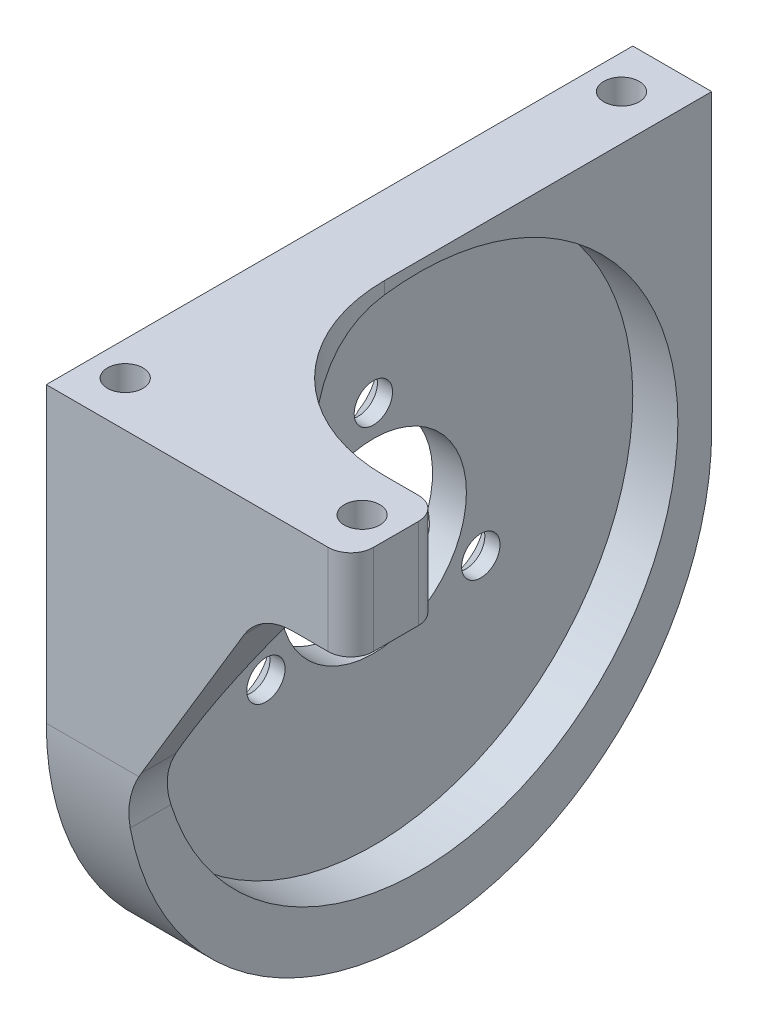
SolidWorks part; units mm, degrees
ref_plane "Plano frontal" through (0, 0, 0) normal (0, 0, 1) x (1, 0, 0)
ref_plane "Plano superior" through (0, 0, 0) normal (0, 1, 0) x (1, 0, 0)
ref_plane "Plano direito" through (0, 0, 0) normal (1, 0, 0) x (0, 0, -1)
sketch "Esboço1" plane through (0, 0, 0) normal (1, 0, 0) x (0, 0, -1)
  line L1 (0, 0) -> (52, 0)
  line L2 (0, 0) -> (0, 52)
  line L3 (0, 52) -> (52, 52)
  line L4 (52, 0) -> (52, 52)
  dimension "D1" = 52
  dimension "D2" = 52
extrude "Ressalto-extrusão1" add sketch "Esboço1" along normal blind 7
sketch "Esboço2" plane through (0, 0, 0) normal (-1, 0, 0) x (0, 0, 1)
  line L1 (-26, 52) -> (-26, 28.1)
  line L2 (-52, 52) -> (0, 52) construction
  circle A0 centre (-26, 28.1) radius 8.25
  dimension "D1" = 16.5
  dimension "D3" = 23.9
extrude "Corte-extrusão1" cut sketch "Esboço2" against normal through all contours A0
sketch "Esboço6" plane through (0, 0, 0) normal (-1, 0, 0) x (0, 0, 1)
  line L1 (-26, 52) -> (-26, 39.1)
  line L2 (-52, 52) -> (0, 52) construction
  circle A0 centre (-26, 28.1) radius 8.25 construction
  point P0 (-26, 39.1)
  dimension "D1" = 11
hole_wizard "Escareado para SFHCS M31" positions "Esboço13" profile "Esboço14" countersink size "M3" standard "Ansi Metric" end condition up to next
sketch "Esboço13" plane through (0, 0, 0) normal (-1, 0, 0) x (0, 0, 1)
  point P0 (-26, 39.1)
sketch "Esboço14" plane through (0, 39.1, -26) normal (0, 1, 0) x (0, 0, 1)
  line L0 (0, 0) -> (0, 7)
  line L1 (0, 7) -> (1.7, 7)
  line L2 (1.7, 7) -> (1.7, 1.66)
  line L3 (1.7, 1.66) -> (3.36, 0)
  line L5 (3.36, 0) -> (0, 0)
  line L6 (-1.7, 1.66) -> (-3.36, 0) construction
  line L11 (0, -6.35) -> (0, 107.95) construction
  dimension "Thru Hole Dia." = 3.4
  dimension "Thru Hole Depth" = 7
  dimension "Near C'Sink Dia." = 6.72
  dimension "Near C'Sink Angle" = 90
pattern_circular "PadrãoCircular1" count 3 over 360 about axis through (0, 28.1, -26) along (-1, 0, 0) of "Escareado para SFHCS M31"
sketch "Esboço27" plane through (7, 0, 0) normal (1, 0, 0) x (0, 0, -1)
  circle A0 centre (26, 28.1) radius 23
  dimension "D1" = 46
extrude "Corte-extrusão5" cut sketch "Esboço27" against normal blind 4
fillet "Filete1" radius 26 2 edges at (3.5, 0, -52) (3.5, 0, 0)
hole_wizard "Furo roscado para conduíte de M3x0.51" positions "Esboço33" profile "Esboço34" tap size "M3x0.5" standard "Helicoil® Metric"
sketch "Esboço33" plane through (0, 52, 0) normal (0, 1, 0) x (1, 0, 0)
  line L0 (0, 52) -> (0, 0) construction
  line L1 (7, 52) -> (0, 52) construction
  line L2 (7, 0) -> (0, 0) construction
  point P0 (3, 48)
  point P2 (3, 4)
  dimension "D1" = 3
  dimension "D2" = 4
  dimension "D3" = 3
  dimension "D4" = 4
cosmetic thread "Rosca de furo1"
cosmetic thread "Rosca de furo2"
sketch "Esboço34" plane through (3, 52, -48) normal (1, 0, 0) x (0, 0, 1)
  line L0 (0, 0) -> (0, 10.9464)
  line L1 (0, 10.9464) -> (1.575, 10)
  line L2 (1.575, 10) -> (1.575, 0)
  line L5 (1.575, 0) -> (0, 0)
  line L10 (0, 10.9464) -> (-1.575, 10) construction
  line L11 (0, -6.35) -> (0, 107.95) construction
  dimension "Tap Drill Dia." = 3.15
  dimension "Tap Drill Depth" = 10
  dimension "Drill Angle" = 118
sketch "Esboço35" plane through (0, 52, 0) normal (0, 1, 0) x (1, 0, 0)
  line L1 (7, 52) -> (27, 52)
  line L2 (7, 52) -> (7, 0)
  line L3 (7, 0) -> (27, 0)
  line L4 (27, 52) -> (27, 0)
  dimension "D1" = 20
  dimension "D2" = 52
extrude "Ressalto-extrusão2" add sketch "Esboço35" against normal blind 8
sketch "Esboço37" plane through (7, 0, 0) normal (1, 0, 0) x (0, 0, -1)
  circle A0 centre (26, 28.1) radius 23
extrude "Corte-extrusão6" cut sketch "Esboço37" along normal through all
chamfer "Chanfro1" distance 12 distance2 20 2 edges at (7, 44, -47.3095) (7, 44, -4.6905) first distance on face at (17, 44, -47.3095) first distance on face at (17, 44, -4.6905)
fillet "Filete2" radius 10 2 edges at (7, 24, -1.7227) (7, 24, -50.2773)
fillet "Filete3" radius 5 2 edges at (19, 44, -4.6905) (19, 44, -47.3095)
ref_plane "Plano1" through (13.5, 0, 0) normal (-1, 0, 0) x (0, 0, 1)
mirror "Espelhar1" about plane through (13.5, 0, 0) normal (-1, 0, 0) of "Furo roscado para conduíte de M3x0.51"
cosmetic thread "Rosca de furo3"
cosmetic thread "Rosca de furo4"
sketch "Esboço39" plane through (0, 52, 0) normal (0, 1, 0) x (1, 0, 0)
  line L0 (7, 26) -> (27, 26) construction
  line L3 (27, 9.381) -> (27, 42.619) construction
  line L4 (7, 4.0499) -> (7, 47.9501) construction
  line L5 (27, 44) -> (7, 44)
  line L6 (27, 44) -> (27, 8)
  line L7 (27, 8) -> (7, 8)
  line L8 (7, 44) -> (7, 8)
  line L9 (27, 44) -> (7, 8) construction
  line L10 (27, 8) -> (7, 44) construction
  point P4 (17, 26)
  dimension "D1" = 36
extrude "Corte-extrusão7" cut sketch "Esboço39" against normal up to next
fillet "Filete5" radius 15 2 edges at (7, 47.2089, -44) (7, 47.2089, -8)
fillet "Filete6" radius 2 4 edges at (27, 48, -44) (27, 48, -52) (27, 48, -8) (27, 48, 0)
sketch "Esboço40" plane through (0, 0, -52) normal (0, 0, 1) x (1, 0, 0)
  line L1 (7, 0) -> (39.2437, 0)
  line L2 (7, 0) -> (7, 53.2303)
  line L3 (7, 53.2303) -> (39.2437, 53.2303)
  line L4 (39.2437, 0) -> (39.2437, 53.2303)
sketch "Esboço43" plane through (0, 0, -52) normal (0, 0, -1) x (-1, 0, 0)
  line L1 (-7, 0) -> (-46.5151, 0)
  line L2 (-7, 0) -> (-7, 58.1026)
  line L3 (-7, 58.1026) -> (-46.5151, 58.1026)
  line L4 (-46.5151, 0) -> (-46.5151, 58.1026)
extrude "Corte-extrusão9" cut sketch "Esboço43" against normal up to next
